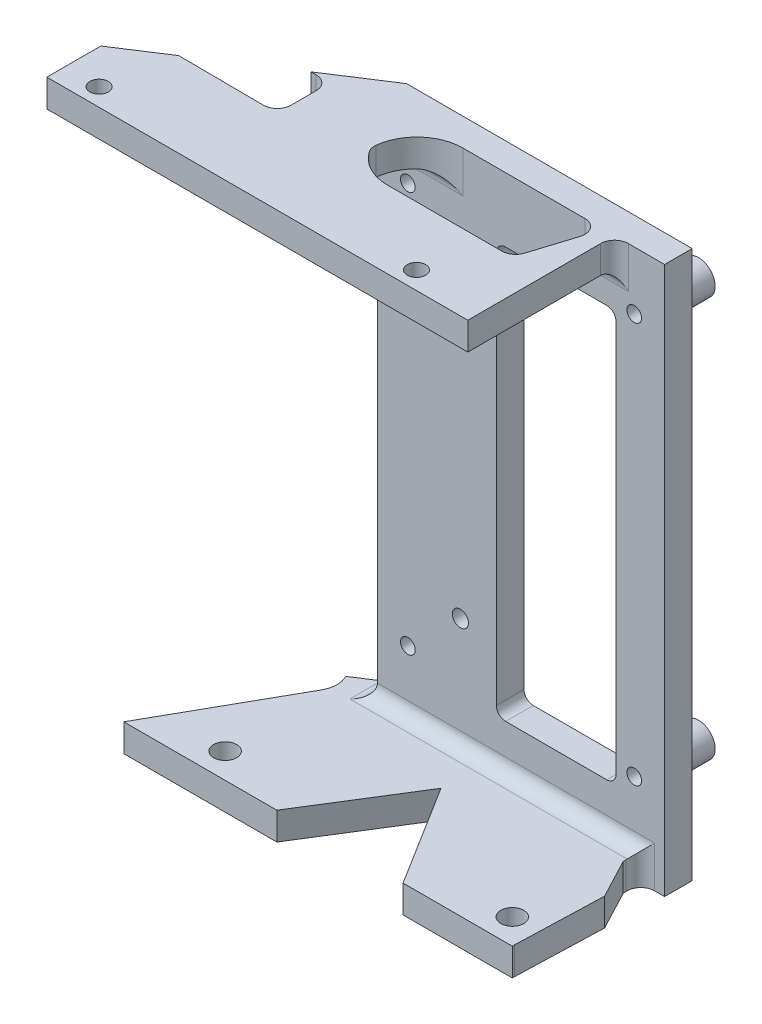
SolidWorks part; units mm, degrees
ref_plane "前视基准面" through (0, 0, 0) normal (0, 0, 1) x (1, 0, 0)
ref_plane "上视基准面" through (0, 0, 0) normal (0, 1, 0) x (1, 0, 0)
ref_plane "右视基准面" through (0, 0, 0) normal (1, 0, 0) x (0, 0, -1)
sketch "草图1" plane through (0, 0, 0) normal (0, 0, 1) x (1, 0, 0)
  line L0 (-17.6638, -32.6168) -> (-20.9904, -38.3988)
  line L1 (-11.423, -36.2074) -> (-14.7496, -41.9893)
  circle A0 centre (-17.87, 46.89) radius 1.6
  circle A1 centre (31.3381, 46.89) radius 1.6
  circle A2 centre (29.093, 5.5908) radius 1.6
  circle A5 centre (31.3381, -40.194) radius 1.6
  circle A6 centre (-17.87, 46.89) radius 3.6
  circle A7 centre (31.3381, 46.89) radius 3.6
  circle A8 centre (29.093, 5.5908) radius 3.6
  circle A9 centre (31.3381, -40.194) radius 3.6
  arc A10 (-11.423, -36.2074) -> (-17.6638, -32.6168) centre (-14.5434, -34.4121) ccw
  arc A11 (-20.9904, -38.3988) -> (-14.7496, -41.9893) centre (-17.87, -40.194) ccw
  circle A12 centre (-14.5434, -34.4121) radius 1.6
  circle A13 centre (-17.87, -40.194) radius 1.6
  dimension "D1" = 2
extrude "凸台-拉伸1" add sketch "草图1" along normal blind 3
sketch "草图2" plane through (0, 0, 3) normal (0, 0, 1) x (1, 0, 0)
  line L0 (-17.87, -43.794) -> (31.3381, -43.794) construction
  line L1 (-21.47, -40.194) -> (-21.47, 46.89) construction
  line L3 (25.375, 45.5) -> (3.375, 45.5)
  line L4 (-17.87, -46.794) -> (31.3381, -46.794)
  line L5 (-17.87, 50.49) -> (31.3381, 50.49) construction
  line L6 (34.9381, 46.89) -> (34.9381, -40.1941) construction
  line L7 (1.375, 34.35) -> (1.375, -37.65)
  line L8 (1.375, 43.5) -> (1.375, -41.794)
  line L10 (27.375, -37.65) -> (27.375, 34.35)
  line L11 (27.375, -41.794) -> (27.375, 43.5)
  line L19 (37.9381, 46.89) -> (37.9381, -40.1941)
  line L20 (-17.87, 53.49) -> (31.3381, 53.49)
  line L21 (-24.47, -40.194) -> (-24.47, 46.89)
  line L22 (3.375, -43.794) -> (25.375, -43.794)
  arc A0 (-20.9904, -38.3988) -> (-14.7496, -41.9893) centre (-17.87, -40.194) ccw construction
  circle A1 centre (31.3381, -40.194) radius 3.6 construction
  circle A2 centre (-17.87, 46.89) radius 3.6 construction
  circle A3 centre (31.3381, 46.89) radius 3.6 construction
  arc A4 (34.9381, 46.89) -> (31.3381, 50.49) centre (31.3381, 46.89) ccw construction
  arc A5 (-17.87, 50.49) -> (-21.47, 46.89) centre (-17.87, 46.89) ccw construction
  arc A6 (-21.47, -40.194) -> (-17.87, -43.794) centre (-17.87, -40.194) ccw construction
  arc A7 (31.3381, -43.794) -> (34.9381, -40.1941) centre (31.3381, -40.194) ccw construction
  arc A16 (31.3381, -46.794) -> (37.9381, -40.1941) centre (31.3381, -40.194) ccw
  arc A17 (37.9381, 46.89) -> (31.3381, 53.49) centre (31.3381, 46.89) ccw
  arc A18 (-17.87, 53.49) -> (-24.47, 46.89) centre (-17.87, 46.89) ccw
  arc A19 (-24.47, -40.194) -> (-17.87, -46.794) centre (-17.87, -40.194) ccw
  arc A20 (1.375, -41.794) -> (3.375, -43.794) centre (3.375, -41.794) ccw
  arc A21 (27.375, -41.794) -> (25.375, -43.794) centre (25.375, -41.794) cw
  arc A22 (27.375, 43.5) -> (25.375, 45.5) centre (25.375, 43.5) ccw
  arc A23 (3.375, 45.5) -> (1.375, 43.5) centre (3.375, 43.5) ccw
  circle A24 centre (-14.5434, -34.4121) radius 1.6 construction
  circle A25 centre (-17.87, -40.194) radius 1.6 construction
  circle A26 centre (31.3381, -40.194) radius 1.6 construction
  circle A27 centre (29.093, 5.5908) radius 1.6 construction
  circle A28 centre (31.3381, 46.89) radius 1.6 construction
  circle A29 centre (-17.87, 46.89) radius 1.6 construction
  circle A30 centre (-14.5434, -34.4121) radius 1.6
  circle A31 centre (-17.87, -40.194) radius 1.6
  circle A32 centre (31.3381, -40.194) radius 1.6
  circle A33 centre (29.093, 5.5908) radius 1.6
  circle A34 centre (31.3381, 46.89) radius 1.6
  circle A35 centre (-17.87, 46.89) radius 1.6
  point P39 (1.375, -43.794)
  point P42 (27.375, -43.794)
  dimension "D4" = 2
  dimension "D1" = 5
  dimension "D2" = 2
  dimension "D3" = 3
extrude "凸台-拉伸2" add sketch "草图2" along normal blind 6
sketch "草图3" plane through (0, 0, 3) normal (0, 0, 1) x (1, 0, 0)
  line L1 (27.375, 2.4272) -> (27.375, 8.7544)
  line L2 (27.375, 2.4272) -> (27.375, 8.7544)
  arc A1 (27.375, 8.7544) -> (27.375, 2.4272) centre (29.093, 5.5908) ccw
  arc A2 (27.375, 8.7544) -> (27.375, 2.4272) centre (29.093, 5.5908) ccw
  dimension "D1" = 0
extrude "切除-拉伸1" cut sketch "草图3" against normal blind 5
sketch "草图4" plane through (0, 0, 9) normal (0, 0, 1) x (1, 0, 0)
  line L0 (-24.47, 3.348) -> (1.375, 3.348) construction
  line L1 (-24.47, 46.89) -> (-24.47, -40.194) construction
  line L2 (1.375, 43.5) -> (1.375, -41.794) construction
  line L3 (-11.5475, 37.348) -> (-11.5475, -30.652) construction
  line L4 (-11.5475, 37.348) -> (-6.5475, 37.348) construction
  line L5 (-6.5475, 37.348) -> (-6.5475, -30.652) construction
  circle A0 centre (-11.5475, 37.348) radius 2.1 construction
  circle A1 centre (-11.5475, -30.652) radius 2.1 construction
  circle A2 centre (-6.5475, 37.348) radius 2.1
  circle A3 centre (-6.5475, -30.652) radius 2.1
  point P9 (-11.5475, 3.348)
sketch "草图5" plane through (0, 0, 9) normal (0, 0, 1) x (1, 0, 0)
  line L1 (-14.6946, 46.89) -> (-16.2823, 49.64)
  line L2 (-16.2823, 49.64) -> (-19.4577, 49.64)
  line L3 (-19.4577, 49.64) -> (-21.0454, 46.89)
  line L4 (-21.0454, 46.89) -> (-19.4577, 44.14)
  line L5 (-19.4577, 44.14) -> (-16.2823, 44.14)
  line L6 (-16.2823, 44.14) -> (-14.6946, 46.89)
  line L7 (34.5136, 46.89) -> (32.9258, 49.64)
  line L8 (32.9258, 49.64) -> (29.7504, 49.64)
  line L9 (29.7504, 49.64) -> (28.1627, 46.89)
  line L10 (28.1627, 46.89) -> (29.7504, 44.14)
  line L11 (29.7504, 44.14) -> (32.9258, 44.14)
  line L12 (32.9258, 44.14) -> (34.5136, 46.89)
  line L19 (-11.368, -34.4121) -> (-12.9557, -31.6621)
  line L20 (-12.9557, -31.6621) -> (-16.1311, -31.6621)
  line L21 (-16.1311, -31.6621) -> (-17.7188, -34.4121)
  line L22 (-17.7188, -34.4121) -> (-16.1311, -37.1621)
  line L23 (-16.1311, -37.1621) -> (-12.9557, -37.1621)
  line L24 (-12.9557, -37.1621) -> (-11.368, -34.4121)
  line L25 (-14.6946, -40.194) -> (-16.2823, -37.444)
  line L26 (-16.2823, -37.444) -> (-19.4577, -37.444)
  line L27 (-19.4577, -37.444) -> (-21.0454, -40.194)
  line L28 (-21.0454, -40.194) -> (-19.4577, -42.944)
  line L29 (-19.4577, -42.944) -> (-16.2823, -42.944)
  line L30 (-16.2823, -42.944) -> (-14.6946, -40.194)
  line L31 (34.5135, -40.194) -> (32.9258, -37.444)
  line L32 (32.9258, -37.444) -> (29.7504, -37.444)
  line L33 (29.7504, -37.444) -> (28.1627, -40.194)
  line L34 (28.1627, -40.194) -> (29.7504, -42.944)
  line L35 (29.7504, -42.944) -> (32.9258, -42.944)
  line L36 (32.9258, -42.944) -> (34.5135, -40.194)
  line L37 (32.2684, 5.5908) -> (30.6807, 8.3408)
  line L38 (30.6807, 8.3408) -> (27.5053, 8.3408)
  line L39 (27.5053, 8.3408) -> (25.9176, 5.5908)
  line L40 (25.9176, 5.5908) -> (27.5053, 2.8408)
  line L41 (27.5053, 2.8408) -> (30.6807, 2.8408)
  line L42 (30.6807, 2.8408) -> (32.2684, 5.5908)
  circle A0 centre (-17.87, 46.89) radius 2.75 construction
  circle A1 centre (31.3381, 46.89) radius 2.75 construction
  circle A3 centre (-14.5434, -34.4121) radius 2.75 construction
  circle A4 centre (-17.87, -40.194) radius 2.75 construction
  circle A5 centre (31.3381, -40.194) radius 2.75 construction
  circle A6 centre (29.093, 5.5908) radius 2.75 construction
sketch "草图9" plane through (0, -59.5, 0) normal (0, 1, 0) x (1, 0, 0)
  line L1 (-31.2106, -60.3759) -> (31.2106, -60.3759)
  circle A0 centre (-31.2106, -55.3759) radius 2.5
  circle A1 centre (31.2106, -55.3759) radius 2.5
  circle A2 centre (-31.2106, -55.3759) radius 5
  circle A3 centre (31.2106, -55.3759) radius 5
sketch "草图10" plane through (0, 0, 9) normal (0, 0, 1) x (1, 0, 0)
  line L0 (-24.47, 46.89) -> (-24.47, -40.194) construction
  line L1 (37.9381, -40.1941) -> (37.9381, 46.89) construction
  line L2 (-24.47, 59.5) -> (-24.47, 46.89)
  line L3 (37.9381, -59.5) -> (37.9381, -40.1941)
  line L4 (-31.2106, -59.5) -> (31.2106, -59.5) construction
  line L5 (-24.47, -59.5) -> (37.9381, -59.5)
  line L6 (-112, 59.5) -> (-120, 59.5) construction
  line L7 (37.9381, 59.5) -> (-24.47, 59.5)
  line L8 (37.9381, 46.89) -> (37.9381, 59.5)
  line L9 (-24.47, -40.194) -> (-24.47, -59.5)
  line L12 (-17.87, -46.794) -> (31.3381, -46.794)
  line L13 (37.9381, -40.1941) -> (37.9381, 46.89)
  line L14 (31.3381, 53.49) -> (-17.87, 53.49)
  line L15 (-24.47, 46.89) -> (-24.47, -40.194)
  line L16 (-17.87, -46.794) -> (31.3381, -46.794)
  line L18 (31.3381, 53.49) -> (-17.87, 53.49)
  arc A4 (-24.47, -40.194) -> (-17.87, -46.794) centre (-17.87, -40.194) ccw
  arc A5 (31.3381, -46.794) -> (37.9381, -40.1941) centre (31.3381, -40.194) ccw
  arc A6 (37.9381, 46.89) -> (31.3381, 53.49) centre (31.3381, 46.89) ccw
  arc A7 (-17.87, 53.49) -> (-24.47, 46.89) centre (-17.87, 46.89) ccw
  arc A8 (-24.47, -40.194) -> (-17.87, -46.794) centre (-17.87, -40.194) ccw
  arc A9 (31.3381, -46.794) -> (37.9381, -40.1941) centre (31.3381, -40.194) ccw
  arc A10 (37.9381, 46.89) -> (31.3381, 53.49) centre (31.3381, 46.89) ccw
  arc A11 (-17.87, 53.49) -> (-24.47, 46.89) centre (-17.87, 46.89) ccw
  dimension "D1" = 0
extrude "凸台-拉伸3" add sketch "草图10" against normal blind 6
sketch "草图12" plane through (0, -59.5, 0) normal (0, 1, 0) x (1, 0, 0)
  line L0 (-31.2106, -60.3759) -> (31.2106, -60.3759) construction
  line L1 (-31.2106, -60.3759) -> (31.2106, -60.3759)
  line L2 (-24.47, -3) -> (-36.087, -54.271)
  line L3 (37.9381, -3) -> (36.2079, -55.5404)
  line L4 (37.9381, -3) -> (-24.47, -3) construction
  line L5 (37.9381, -3) -> (-24.47, -3)
  circle A0 centre (31.2106, -55.3759) radius 5 construction
  circle A1 centre (31.2106, -55.3759) radius 2.5 construction
  circle A2 centre (-31.2106, -55.3759) radius 2.5 construction
  circle A3 centre (-31.2106, -55.3759) radius 5 construction
  arc A4 (31.2106, -60.3759) -> (36.2079, -55.5404) centre (31.2106, -55.3759) ccw
  circle A5 centre (31.2106, -55.3759) radius 2.5
  circle A6 centre (-31.2106, -55.3759) radius 2.5
  arc A7 (-36.087, -54.271) -> (-31.2106, -60.3759) centre (-31.2106, -55.3759) ccw
extrude "凸台-拉伸4" add sketch "草图12" along normal blind 6
sketch "草图13" plane through (0, 59.5, 0) normal (0, -1, 0) x (1, 0, 0)
  line L0 (-57, 61.4859) -> (12, 61.4859)
  line L1 (-24.47, 3) -> (-60.6787, 54.3941)
  line L2 (37.9381, 3.0016) -> (16.1911, 58.6245)
  line L3 (-24.47, 3) -> (37.9381, 3.0016)
  circle A0 centre (-57, 56.9859) radius 2
  circle A1 centre (12, 56.9859) radius 2
  arc A4 (-57, 61.4859) -> (-60.6787, 54.3941) centre (-57, 56.9859) ccw
  arc A5 (16.1911, 58.6245) -> (12, 61.4859) centre (12, 56.9859) ccw
extrude "凸台-拉伸5" add sketch "草图13" along normal blind 6
sketch "草图15" plane through (-24.47, 0, 0) normal (-1, 0, 0) x (0, 0, 1)
  line L0 (61.4859, 53.5) -> (61.4859, 59.5) construction
  line L1 (3, 53.5) -> (61.4859, 53.5)
  line L2 (3, 53.5) -> (3, 59.5)
  line L3 (3, 59.5) -> (61.4859, 59.5)
  line L4 (61.4859, 53.5) -> (61.4859, 59.5)
  dimension "D1" = 6
extrude "凸台-拉伸7" add sketch "草图15" along normal blind 40
sketch "草图16" plane through (0, 59.5, 0) normal (0, 1, 0) x (1, 0, 0)
  line L0 (12, -56.9859) -> (-67.8355, -56.9859) construction
  circle A0 centre (-57, -56.9859) radius 2
  dimension "D1" = 69
extrude "切除-拉伸5" cut sketch "草图16" against normal blind 40
fillet "圆角1" radius 5 1 edges at (-64.47, 56.5, 61.4859)
sketch "草图18" plane through (0, 59.5, 0) normal (0, 1, 0) x (1, 0, 0)
  line L0 (12, -56.9859) -> (12, -36.9859)
  line L1 (12, -36.9859) -> (-72.3516, -36.9859) construction
  circle A0 centre (12, -36.9859) radius 2
  circle A1 centre (-57, -36.9859) radius 2
  dimension "D2" = 69
  dimension "D1" = 20
extrude "切除-拉伸6" cut sketch "草图18" against normal blind 40 contours L1 L0 A0 | L0 L1 A0 | L1 A1 | A1 L1 region at (11.1512, 59.5, 37.8347) region at (-57, 59.5, 37.8347) region at (-57, 59.5, 36.137) region at (12.2829, 59.5, 36.7029)
sketch "草图19" plane through (0, -59.5, 0) normal (0, -1, 0) x (1, 0, 0)
  line L0 (-40.5722, 35.3759) -> (48.8178, 35.3759) construction
  circle A0 centre (31.2106, 55.3759) radius 2.5 construction
  circle A1 centre (-31.2106, 55.3759) radius 2.5 construction
  circle A2 centre (31.2106, 55.3759) radius 2.5
  circle A3 centre (-31.2106, 55.3759) radius 2.5
  dimension "D1" = 20
sketch "草图21" plane through (-24.47, 0, 0) normal (-1, 0, 0) x (0, 0, 1)
  line L1 (3, -53.5) -> (60.3759, -53.5)
  line L2 (3, -53.5) -> (3, -59.5)
  line L3 (3, -59.5) -> (60.3759, -59.5)
  line L4 (60.3759, -53.5) -> (60.3759, -59.5)
extrude "凸台-拉伸8" add sketch "草图21" along normal blind 40
sketch "草图24" plane through (0, -59.5, 0) normal (0, -1, 0) x (1, 0, 0)
  line L0 (-31.2106, 55.3759) -> (31.2106, 55.3759) construction
  line L1 (-22.0643, 35.3759) -> (19.0684, 35.3759) construction
  line L2 (-40.5722, 35.3759) -> (48.8178, 35.3759) construction
  circle A0 centre (31.2106, 35.3759) radius 2.5
  circle A1 centre (-31.2106, 35.3759) radius 2.5
  dimension "D1" = 20
extrude "切除-拉伸7" cut sketch "草图24" along normal blind 12 and the other way blind 26
sketch "草图25" plane through (0, -59.5, 0) normal (0, -1, 0) x (1, 0, 0)
  line L0 (-64.47, 60.3759) -> (31.2106, 60.3759) construction
  line L1 (-69.8102, 67.4831) -> (48.8057, 67.4831)
  line L2 (-69.8102, 67.4831) -> (-69.8102, 40.3759)
  line L3 (-69.8102, 40.3759) -> (48.8057, 40.3759)
  line L4 (48.8057, 67.4831) -> (48.8057, 40.3759)
  dimension "D1" = 20
extrude "切除-拉伸9" cut sketch "草图25" against normal blind 130 contours L2 L3 L4 L1
sketch "草图26" plane through (37.9381, 0, 0) normal (1, 0, 0) x (0, 0, -1)
  line L1 (-3, 9.1908) -> (0, 9.1908)
  line L2 (-3, 9.1908) -> (-3, 1.9908)
  line L3 (-3, 1.9908) -> (0, 1.9908)
  line L4 (0, 9.1908) -> (0, 1.9908)
extrude "切除-拉伸10" cut sketch "草图26" against normal blind 13
sketch "草图27" plane through (0, -59.5, 0) normal (0, -1, 0) x (1, 0, 0)
  line L0 (-64.47, 3) -> (-24.1614, 3)
  line L1 (-64.47, 3) -> (37.9381, 3) construction
  line L2 (-24.1614, 3) -> (-64.47, 29.1487)
  line L3 (-64.47, 3) -> (-64.47, 40.3759) construction
  line L4 (-64.47, 3) -> (-64.47, 29.1487)
extrude "切除-拉伸11" cut sketch "草图27" against normal blind 153
sketch "草图28" plane through (0, 59.5, 0) normal (0, 1, 0) x (1, 0, 0)
  line L0 (37.9381, -9) -> (35.5929, -9)
  line L1 (35.5929, -9) -> (23.3258, -40.3759)
  line L2 (23.3258, -40.3759) -> (36.7073, -40.3759)
  line L3 (36.7073, -40.3759) -> (37.7405, -9)
  line M4 (23.3258, -40.3759) -> (35.5929, -9)
  line M5 (35.5929, -9) -> (37.9381, -9)
extrude "凸台-拉伸9" add sketch "草图28" against normal up to surface (6 mm away) contours L2 L3 M5 M4 region at (32.5398, 59.5, 28.4708) up to face at (-19.8269, 53.5, 21.8501)
sketch "草图29" plane through (0, 53.5, 0) normal (0, -1, 0) x (1, 0, 0)
  line L1 (-64.47, 40.3759) -> (36.7073, 40.3759) construction
  line L2 (14.2169, 40.3759) -> (36.7073, 40.3759)
  line L3 (36.7073, 40.3759) -> (37.7405, 9)
  line L5 (37.7405, 9) -> (25.2907, 9)
  line L6 (-24.47, 9) -> (37.7405, 9) construction
  line L7 (25.2907, 9) -> (14.2169, 40.3759)
extrude "切除-拉伸12" cut sketch "草图29" against normal blind 10
sketch "草图30" plane through (0, 0, 0) normal (0, 0, -1) x (-1, 0, 0)
  line L0 (17.6638, -32.6168) -> (20.9904, -38.3988) construction
  line L1 (14.7496, -41.9893) -> (11.423, -36.2074) construction
  line L2 (17.6638, -32.6168) -> (20.9904, -38.3988)
  line L3 (14.7496, -41.9893) -> (11.423, -36.2074)
  circle A0 centre (17.87, 46.89) radius 3.6 construction
  circle A1 centre (17.87, 46.89) radius 1.6 construction
  arc A2 (14.7496, -41.9893) -> (20.9904, -38.3988) centre (17.87, -40.194) ccw construction
  arc A3 (17.6638, -32.6168) -> (11.423, -36.2074) centre (14.5434, -34.4121) ccw construction
  circle A4 centre (17.87, -40.194) radius 1.6 construction
  circle A5 centre (14.5434, -34.4121) radius 1.6 construction
  circle A6 centre (-31.3381, 46.89) radius 3.6 construction
  circle A7 centre (-31.3381, 46.89) radius 1.6 construction
  circle A8 centre (-31.3381, -40.194) radius 1.6 construction
  circle A9 centre (-31.3381, -40.194) radius 3.6 construction
  circle A10 centre (17.87, 46.89) radius 3.6
  circle A11 centre (17.87, 46.89) radius 1.6
  arc A12 (14.7496, -41.9893) -> (20.9904, -38.3988) centre (17.87, -40.194) ccw
  arc A13 (17.6638, -32.6168) -> (11.423, -36.2074) centre (14.5434, -34.4121) ccw
  circle A14 centre (17.87, -40.194) radius 1.6
  circle A15 centre (14.5434, -34.4121) radius 1.6
  circle A16 centre (-31.3381, 46.89) radius 3.6
  circle A17 centre (-31.3381, 46.89) radius 1.6
  circle A18 centre (-31.3381, -40.194) radius 1.6
  circle A19 centre (-31.3381, -40.194) radius 3.6
extrude "凸台-拉伸10" add sketch "草图30" along normal blind 5
sketch "草图31" plane through (0, 0, 40.3759) normal (0, 0, 1) x (1, 0, 0)
  line L0 (-64.47, 53.5) -> (14.2169, 53.5) construction
  line L1 (14.2169, 53.5) -> (14.2169, 59.5) construction
  line L2 (14.2169, 59.5) -> (-64.47, 59.5) construction
  line L3 (-64.47, 59.5) -> (-64.47, 53.5) construction
  line L4 (36.7073, -53.5) -> (-64.47, -53.5) construction
  line L5 (-64.47, -53.5) -> (-64.47, -59.5) construction
  line L6 (-64.47, -59.5) -> (36.7073, -59.5) construction
  line L7 (36.7073, -59.5) -> (36.7073, -53.5) construction
  line L8 (-64.47, 53.5) -> (14.2169, 53.5)
  line L9 (14.2169, 53.5) -> (14.2169, 59.5)
  line L10 (14.2169, 59.5) -> (-64.47, 59.5)
  line L11 (-64.47, 59.5) -> (-64.47, 53.5)
  line L12 (36.7073, -53.5) -> (-64.47, -53.5)
  line L13 (-64.47, -53.5) -> (-64.47, -59.5)
  line L14 (-64.47, -59.5) -> (36.7073, -59.5)
  line L15 (36.7073, -59.5) -> (36.7073, -53.5)
extrude "凸台-拉伸11" add sketch "草图31" along normal blind 15
sketch "草图32" plane through (0, -59.5, 0) normal (0, -1, 0) x (1, 0, 0)
  circle A0 centre (31.2106, 35.3759) radius 2.5 construction
  circle A1 centre (-31.2106, 35.3759) radius 2.5 construction
  circle A2 centre (31.2106, 35.3759) radius 2.5
  circle A3 centre (-31.2106, 35.3759) radius 2.5
  circle A4 centre (31.2106, 51.3759) radius 2.5
  circle A5 centre (-31.2106, 51.3759) radius 2.5
  dimension "D1" = 5
  dimension "D3" = 16
  dimension "D2" = 16
extrude "切除-拉伸13" cut sketch "草图32" against normal blind 15
sketch "草图34" plane through (14.2169, 0, 0) normal (1, 0, 0) x (0, 0, -1)
  line L0 (-9, 59.5) -> (-40.3759, 59.5) construction
  line L1 (-40.3759, 53.5) -> (-9, 53.5) construction
  line L2 (-9, 53.5) -> (-9, 59.5) construction
  line L3 (-40.3759, 59.5) -> (-55.3759, 59.5) construction
  line L4 (-55.3759, 59.5) -> (-55.3759, 53.5) construction
  line L5 (-55.3759, 53.5) -> (-40.3759, 53.5) construction
  line L6 (-9, 59.5) -> (-40.3759, 59.5)
  line L7 (-40.3759, 53.5) -> (-9, 53.5)
  line L8 (-9, 53.5) -> (-9, 59.5)
  line L9 (-40.3759, 59.5) -> (-55.3759, 59.5)
  line L10 (-55.3759, 59.5) -> (-55.3759, 53.5)
  line L11 (-55.3759, 53.5) -> (-40.3759, 53.5)
extrude "凸台-拉伸12" add sketch "草图34" along normal blind 3
sketch "草图35" plane through (0, 59.5, 0) normal (0, 1, 0) x (1, 0, 0)
  circle A0 centre (12, -36.9859) radius 2 construction
  circle A1 centre (-57, -36.9859) radius 2 construction
  circle A2 centre (12, -36.9859) radius 2
  circle A3 centre (-57, -36.9859) radius 2
  circle A4 centre (-57, -52.9859) radius 2
  circle A5 centre (12, -52.9859) radius 2
  dimension "D1" = 16
  dimension "D2" = 16
extrude "切除-拉伸14" cut sketch "草图35" against normal blind 23
sketch "草图37" plane through (0, 0, 55.3759) normal (0, 0, 1) x (1, 0, 0)
  line L0 (36.7073, -59.5) -> (36.7073, -53.5) construction
  line L1 (36.7073, -53.5) -> (-64.47, -53.5) construction
  line L2 (-64.47, -53.5) -> (-64.47, -59.5) construction
  line L3 (-64.47, -59.5) -> (36.7073, -59.5) construction
  line L4 (-64.47, 59.5) -> (-64.47, 53.5) construction
  line L5 (-64.47, 53.5) -> (17.2169, 53.5) construction
  line L6 (17.2169, 53.5) -> (17.2169, 59.5) construction
  line L7 (17.2169, 59.5) -> (-64.47, 59.5) construction
  line L8 (36.7073, -59.5) -> (36.7073, -53.5)
  line L9 (36.7073, -53.5) -> (-64.47, -53.5)
  line L10 (-64.47, -53.5) -> (-64.47, -59.5)
  line L11 (-64.47, -59.5) -> (36.7073, -59.5)
  line L12 (-64.47, 59.5) -> (-64.47, 53.5)
  line L13 (-64.47, 53.5) -> (17.2169, 53.5)
  line L14 (17.2169, 53.5) -> (17.2169, 59.5)
  line L15 (17.2169, 59.5) -> (-64.47, 59.5)
extrude "凸台-拉伸13" add sketch "草图37" along normal blind 3
sketch "草图39" plane through (0, -59.5, 0) normal (0, -1, 0) x (1, 0, 0)
  line L0 (-57.6059, 58.3759) -> (-32.2712, 13.3894)
  line L1 (-64.47, 58.3759) -> (36.7073, 58.3759) construction
  line L2 (-42.5688, 10.7) -> (-64.47, 29.1487)
  line L3 (-64.47, 29.1487) -> (-64.47, 58.3759)
  line L4 (-64.47, 58.3759) -> (-57.6059, 58.3759)
  arc A0 (-42.5688, 10.7) -> (-32.2818, 13.4083) centre (-37.0688, 10.7) ccw
  line M3 (-64.47, 29.1487) -> (-24.1614, 3)
  line M10 (36.7073, 58.3759) -> (-64.47, 58.3759)
  line M11 (-64.47, 58.3759) -> (-64.47, 29.1487)
extrude "切除-拉伸15" cut sketch "草图39" against normal blind 13 contours A0 L0 M3 M10 M11 region at (-51.9137, -59.5, 33.7319)
sketch "草图40" plane through (0, -59.5, 0) normal (0, -1, 0) x (1, 0, 0)
  line L0 (13.4905, 59.6438) -> (4.7976, 44.1367)
  line L1 (4.7976, 44.1367) -> (31.8764, 92.4418) construction
  line L2 (-4.7976, 44.1367) -> (-13.4702, 59.6075)
  line L3 (-31.8764, 92.4418) -> (-4.7976, 44.1367) construction
  line L5 (13.4905, 59.6438) -> (-13.4702, 59.6075)
  arc A0 (-4.7976, 44.1367) -> (4.7976, 44.1367) centre (0, 46.8261) ccw
extrude "切除-拉伸16" cut sketch "草图40" against normal blind 13
sketch "草图41" plane through (0, -59.5, 0) normal (0, -1, 0) x (1, 0, 0)
  line L1 (37.9381, 6.0008) -> (37.3312, 21.4305)
  line L2 (37.9381, 3.0016) -> (37.9381, 9) construction
  line L3 (36.7073, 40.3759) -> (37.7405, 9) construction
  line L4 (32.843, 12.9317) -> (37.3312, 21.4305)
  circle A0 centre (37.0688, 10.7) radius 4.7789
  line M13 (37.7405, 9) -> (36.7073, 40.3759)
extrude "切除-拉伸17" cut sketch "草图41" against normal blind 13 contours A0 L4 M13 region at (36.1255, -59.5, 17.1554)
sketch "草图42" plane through (0, -59.5, 0) normal (0, -1, 0) x (1, 0, 0)
  line L0 (37.9381, 9) -> (37.5279, 15.4568)
  line L1 (37.9381, 9) -> (32.557, 9)
  line L2 (32.557, 9) -> (32.843, 12.9317)
  arc A0 (32.843, 12.9317) -> (37.5279, 15.4568) centre (37.0688, 10.7) cw
extrude "切除-拉伸18" cut sketch "草图42" against normal blind 13
sketch "草图43" plane through (0, 59.5, 0) normal (0, 1, 0) x (1, 0, 0)
  line L0 (-64.47, -58.3759) -> (-64.47, -29.1487) construction
  line L2 (-64.47, -42.0739) -> (-34.2724, -42.0739)
  line L3 (-64.47, -42.0739) -> (-64.47, -26.9795)
  line L4 (-64.47, -26.9795) -> (-34.2724, -26.9795)
  line L5 (-34.2724, -42.0739) -> (-34.2724, -26.9795)
  line L8 (-9.9513, -42.8051) -> (18.6089, -42.8051)
  line L9 (-9.9513, -42.8051) -> (-9.9513, -28.5406)
  line L10 (-9.9513, -28.5406) -> (18.6089, -28.5406)
  line L11 (18.6089, -42.8051) -> (18.6089, -28.5406)
sketch "草图44" plane through (0, 0, 9) normal (0, 0, 1) x (1, 0, 0)
  circle A0 centre (29.093, 5.5908) radius 1.6
extrude "凸台-拉伸14" add sketch "草图44" against normal up to surface (6 mm away) up to face at (14.375, 0.853, 3)
sketch "草图45" plane through (0, 0, 9) normal (0, 0, 1) x (1, 0, 0)
  circle A0 centre (-14.5434, -34.4121) radius 1.6
extrude "凸台-拉伸15" add sketch "草图45" against normal up to surface (6 mm away) up to face at (14.375, 0.853, 3)
sketch "草图46" plane through (0, 0, 9) normal (0, 0, 1) x (1, 0, 0)
  line L0 (58.4405, 3.348) -> (-68.4523, 3.348) construction
  circle A0 centre (-6.4461, -29.3385) radius 1.75
  circle A2 centre (-6.4461, 36.0345) radius 1.75
  dimension "D1" = 3.5
extrude "切除-拉伸20" cut sketch "草图46" against normal blind 10
sketch "草图47" plane through (0, 0, -5) normal (0, 0, -1) x (-1, 0, 0)
  line L2 (20.9904, -38.3988) -> (17.6638, -32.6168)
  line L3 (11.423, -36.2074) -> (14.7496, -41.9893)
  line L4 (20.9904, -38.3988) -> (17.6638, -32.6168)
  line L5 (11.423, -36.2074) -> (14.7496, -41.9893)
  arc A0 (20.9904, -38.3988) -> (14.7496, -41.9893) centre (17.87, -40.194) ccw
  arc A3 (14.7496, -41.9893) -> (20.9904, -38.3988) centre (17.87, -40.194) ccw
  arc A4 (17.6638, -32.6168) -> (11.423, -36.2074) centre (14.5434, -34.4121) ccw
  arc A6 (17.6638, -32.6168) -> (11.423, -36.2074) centre (14.5434, -34.4121) ccw
  dimension "D1" = 0
extrude "切除-拉伸21" cut sketch "草图47" against normal up to surface (8 mm away) up to face at (-4.6961, -29.3385, 3)
sketch "草图49" plane through (0, 59.5, 0) normal (0, 1, 0) x (1, 0, 0)
sketch "草图50" plane through (0, -59.5, 0) normal (0, -1, 0) x (1, 0, 0)
  line L1 (-85.4786, 78.8914) -> (42.75, 78.8914)
  line L2 (-85.4786, 78.8914) -> (-85.4786, 40.8759)
  line L3 (-85.4786, 40.8759) -> (42.75, 40.8759)
  line L4 (42.75, 78.8914) -> (42.75, 40.8759)
  arc A0 (45.2687, 40.6698) -> (45.2687, 10.0819) centre (42.75, 25.3759) ccw construction
extrude "切除-拉伸22" cut sketch "草图50" against normal blind 279
sketch "草图51" plane through (0, 59.5, 0) normal (0, 1, 0) x (1, 0, 0)
  line L1 (-32.6465, -11.1645) -> (-32.6465, -22.6378)
  line L2 (-32.6465, -22.6378) -> (-54.1992, -22.4859)
  line L3 (-64.47, -29.1487) -> (-24.1614, -3) construction
  line L4 (-40, -22.4859) -> (-85, -22.4859) construction
  line L6 (-32.6465, -11.1645) -> (-42.5605, -11.1645)
  line L7 (-42.5605, -11.1645) -> (-54.1992, -22.4859)
  line L8 (37.9381, -9) -> (25.2907, -9) construction
  line L9 (-15.9252, -24.171) -> (26.1747, -24.171)
  line L10 (-15.9252, -24.171) -> (-15.9252, -9)
  line L11 (-15.9252, -9) -> (26.1747, -9)
  line L12 (26.1747, -24.171) -> (26.1747, -9)
  line L13 (5.1248, -9) -> (5.1248, -24.171) construction
  line L14 (-15.9252, -16.5855) -> (26.1747, -16.5855) construction
  point P0 (5.1248, -16.5855)
extrude "切除-拉伸26" cut sketch "草图51" against normal blind 13
sketch "草图52" plane through (0, -59.5, 0) normal (0, -1, 0) x (1, 0, 0)
  line L0 (12.9563, 40.8759) -> (-14.4705, 40.8759)
  line L1 (-47.7506, 40.8759) -> (36.7073, 40.8759) construction
  line L2 (-14.4705, 40.8759) -> (-0.7571, 18.8972)
  line L3 (-0.7571, 18.8972) -> (12.9563, 40.8759)
extrude "切除-拉伸27" cut sketch "草图52" against normal blind 13
fillet "圆角2" radius 10 1 edges at (-15.9252, 56.5, 9)
fillet "圆角3" radius 10 1 edges at (-15.9252, 56.5, 24.171)
fillet "圆角4" radius 3 1 edges at (-15.9252, 56.5, 19)
sketch "草图53" plane through (0, 59.5, 0) normal (0, 1, 0) x (1, 0, 0)
  line L0 (19.9362, -24.171) -> (24.7018, -9)
  line L1 (37.9381, -9) -> (-5.9252, -9) construction
  line L2 (24.7018, -9) -> (27.0445, -9)
  line L3 (27.0445, -9) -> (27.0445, -40.8759)
  line L4 (36.7073, -40.8759) -> (12.9563, -40.8759) construction
  line L5 (27.0445, -40.8759) -> (17.2169, -40.8759)
  line L6 (17.2169, -40.8759) -> (17.2169, -31.8758)
  line L7 (17.2169, -31.8758) -> (19.9362, -24.171)
extrude "凸台-拉伸16" add sketch "草图53" against normal up to surface (6 mm away) up to face at (-21.7622, 53.5, 21.1164)
fillet "圆角5" radius 3 2 edges at (19.9362, 56.5, 24.171) (24.7018, 56.5, 9)
fillet "圆角6" radius 3 2 edges at (-32.6465, 56.5, 22.6378) (-32.6465, 56.5, 11.1645)
fillet "圆角7" radius 3 7 edges at (-15.1976, 53.5, 9) (-24.47, 53.5, 6.1001) (-24.47, -53.5, 6.1001) (32.557, -56.5, 9) (4.0435, -53.5, 9) (23.8297, 53.5, 9) (27.0445, 56.5, 9)
